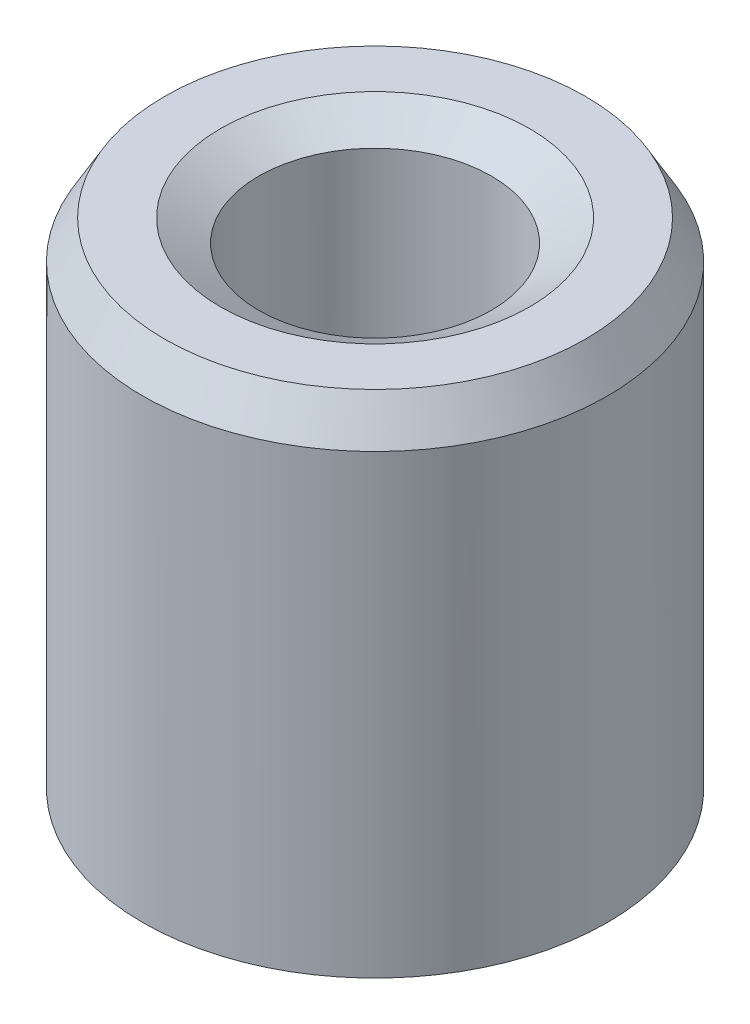
SolidWorks part; units mm, degrees
ref_plane "Front Plane" through (0, 0, 0) normal (0, 0, 1) x (1, 0, 0)
ref_plane "Top Plane" through (0, 0, 0) normal (0, 1, 0) x (1, 0, 0)
ref_plane "Right Plane" through (0, 0, 0) normal (1, 0, 0) x (0, 0, -1)
sketch "Sketch1" plane through (0, 0, 0) normal (0, 1, 0) x (1, 0, 0)
  circle A0 centre (0, 0) radius 12.5
  dimension "SLEEVE_OD" = 25
extrude "Boss-Extrude1" add sketch "Sketch1" along normal blind 27.7689
sketch "Sketch2" plane through (0, 0, 0) normal (0, 1, 0) x (1, 0, 0)
  circle A0 centre (0, 0) radius 6.2583
  dimension "BORE_D" = 12.5165
extrude "Cut-Extrude1" cut sketch "Sketch2" along normal through all
chamfer "Chamfer1" distance 2.0533 angle 30 4 edges at (0, 27.7689, 6.2583) (0, 0, 6.2583) (0, 0, 12.5) (0, 27.7689, 12.5) first distance on face at (0, 27.7689, 6.2583) first distance on face at (0, 0, 6.2583) first distance on face at (0, 27.7689, 12.5)
